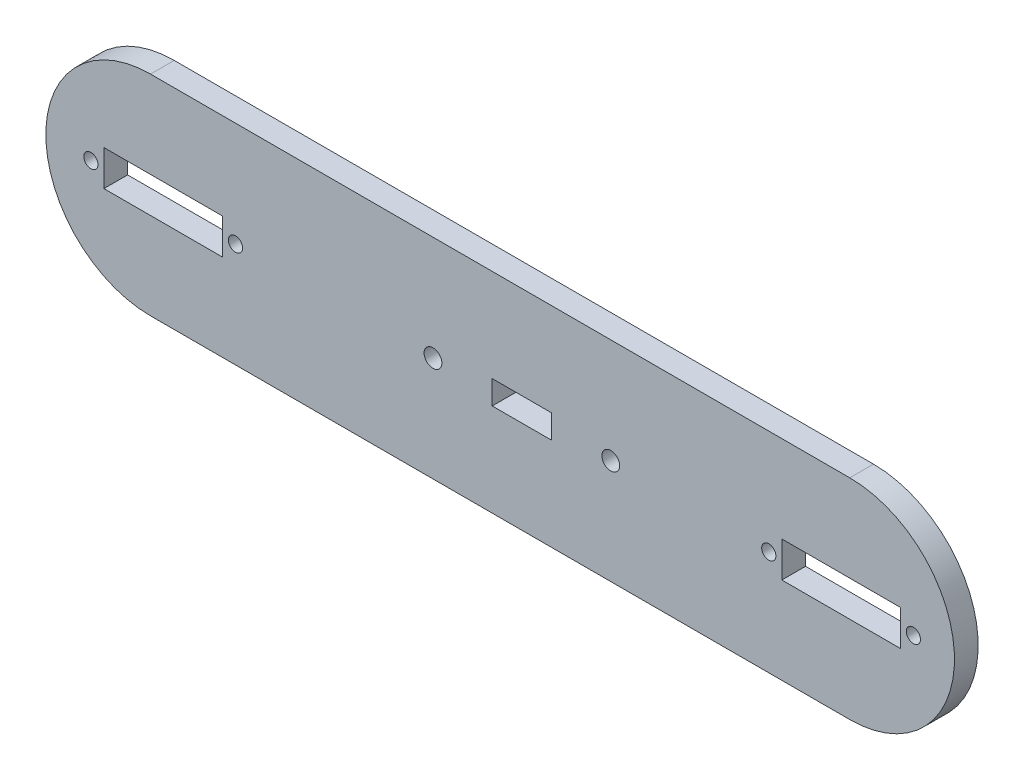
SolidWorks part; units mm, degrees
material "Balsa"
ref_plane "Plano frontal" through (0, 0, 0) normal (0, 0, 1) x (1, 0, 0)
ref_plane "Plano superior" through (0, 0, 0) normal (0, 1, 0) x (1, 0, 0)
ref_plane "Plano direito" through (0, 0, 0) normal (1, 0, 0) x (0, 0, -1)
sketch "Esboço1" plane through (0, 0, 0) normal (0, 0, 1) x (1, 0, 0)
  line L0 (-94, 26.5) -> (83, 26.5)
  line L1 (-94, -26.5) -> (83, -26.5)
  line L2 (-94, 0) -> (-20.25, 0) construction
  line L3 (-22.5, 0) -> (22.5, 0) construction
  line L4 (0, 11.6249) -> (0, -21.7831) construction
  line L6 (-109.1, 0) -> (-72.5, 0) construction
  line L7 (-7.5, -3) -> (7.5, -3)
  line L8 (-7.5, -3) -> (-7.5, 3)
  line L9 (-7.5, 3) -> (7.5, 3)
  line L10 (7.5, -3) -> (7.5, 3)
  line L11 (-7.5, -3) -> (7.5, 3) construction
  line L12 (-7.5, 3) -> (7.5, -3) construction
  line L13 (62.5, 0) -> (99.1, 0) construction
  line L14 (-105.8, -4.5) -> (-75.8, -4.5)
  line L16 (-105.8, 4.5) -> (-75.8, 4.5)
  line L17 (-75.8, -4.5) -> (-75.8, 4.5)
  line L18 (-105.8, -4.5) -> (-75.8, 4.5) construction
  line L19 (-105.8, 4.5) -> (-75.8, -4.5) construction
  line L21 (65.8, -4.5) -> (95.8, -4.5)
  line L22 (65.8, -4.5) -> (65.8, 4.5)
  line L23 (65.8, 4.5) -> (95.8, 4.5)
  line L24 (95.8, -4.5) -> (95.8, 4.5)
  line L25 (65.8, -4.5) -> (95.8, 4.5) construction
  line L26 (65.8, 4.5) -> (95.8, -4.5) construction
  line L27 (-105.8, 4.5) -> (-105.8, -4.5)
  arc A0 (83, -26.5) -> (83, 26.5) centre (83, 0) ccw
  arc A1 (-94, 26.5) -> (-94, -26.5) centre (-94, 0) ccw
  circle A4 centre (-22.5, 0) radius 2.25
  circle A5 centre (22.5, 0) radius 2.25
  circle A6 centre (-109.1, 0) radius 1.8
  circle A7 centre (-72.5, 0) radius 1.8
  circle A8 centre (62.5, 0) radius 1.8
  circle A9 centre (99.1, 0) radius 1.8
  point P8 (0, 0)
  point P19 (0, 0)
  point P24 (0, 0)
  point P29 (-90.8, 0)
  point P34 (80.8, 0)
  point P39 (0, 0)
  point P40 (51.3374, 3.7981)
  point P41 (-96.2887, 6.5)
  point P42 (0, 0)
  point P43 (-103.9311, -6.0199)
  point P44 (20.1799, 0)
  point P45 (23.4434, 0)
  point P46 (0, 0)
  dimension "D1" = 4.5
  dimension "D5" = 15
  dimension "D6" = 26.5
  dimension "D7" = 3.6
  dimension "D2" = 45
  dimension "D3" = 83
  dimension "D4" = 94
  dimension "D8" = 36.6
  dimension "D9" = 50
  dimension "D10" = 6
  dimension "D11" = 9
  dimension "D12" = 30
  dimension "D13" = 40
extrude "Ressalto-extrusão1" add sketch "Esboço1" along normal blind 6
